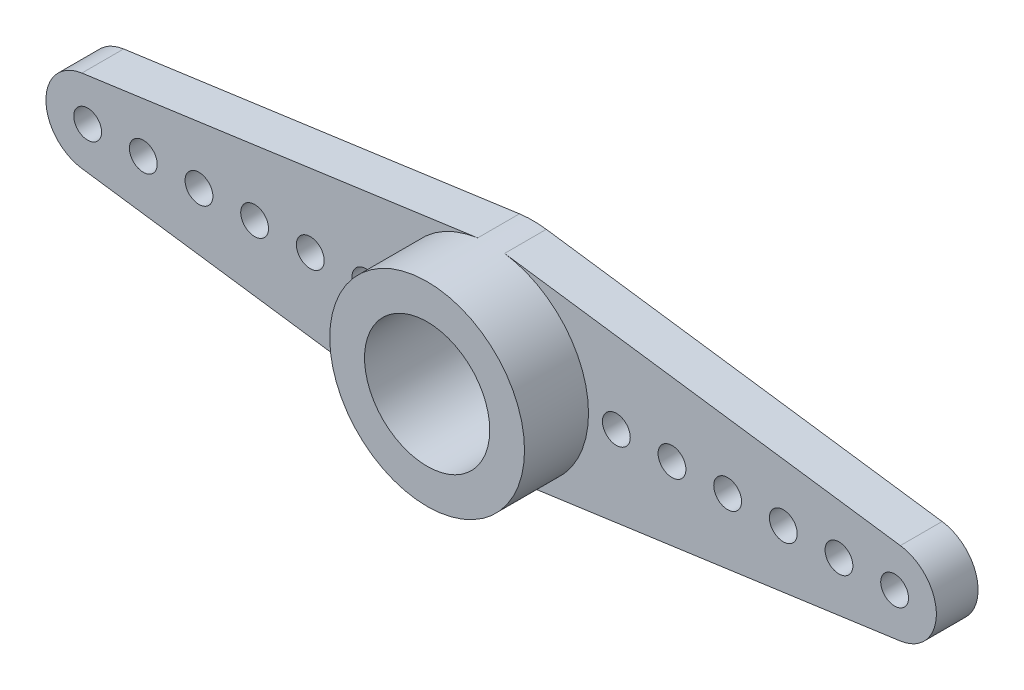
SolidWorks part; units mm, degrees
ref_plane "前视基准面" through (0, 0, 0) normal (0, 0, 1) x (1, 0, 0)
ref_plane "上视基准面" through (0, 0, 0) normal (0, 1, 0) x (1, 0, 0)
ref_plane "右视基准面" through (0, 0, 0) normal (1, 0, 0) x (0, 0, -1)
sketch "草图1" plane through (0, 0, 0) normal (0, 0, 1) x (1, 0, 0)
  line L0 (0, 0) -> (0, -2.5508) construction
  line L1 (-14.5, 0) -> (0, 0) construction
  line L2 (-14.7069, 1.4857) -> (-0.4828, 3.4665)
  line L3 (-14.7069, -1.4857) -> (-0.4828, -3.4665)
  line L4 (14.7069, 1.4857) -> (0.4828, 3.4665)
  line L5 (14.7069, -1.4857) -> (0.4828, -3.4665)
  arc A0 (-0.4828, -3.4665) -> (0.4828, -3.4665) centre (0, 0) ccw
  arc A1 (-14.7069, 1.4857) -> (-14.7069, -1.4857) centre (-14.5, 0) ccw
  arc A2 (14.7069, 1.4857) -> (14.7069, -1.4857) centre (14.5, 0) cw
  arc A3 (0.4828, 3.4665) -> (-0.4828, 3.4665) centre (0, 0) ccw
  point P1 (16, 0)
  point P4 (-16, 0)
  dimension "D1" = 7
  dimension "D3" = 3
  dimension "D2" = 14.5
  dimension "D4" = 32
extrude "凸台-拉伸1" add sketch "草图1" along normal blind 1.5
sketch "草图2" plane through (0, 0, 1.5) normal (0, 0, 1) x (1, 0, 0)
  circle A0 centre (0, 0) radius 3.5
  dimension "D1" = 7
extrude "凸台-拉伸2" add sketch "草图2" along normal blind 2.3
sketch "草图3" plane through (0, 0, 3.8) normal (0, 0, 1) x (1, 0, 0)
  circle A0 centre (0, 0) radius 2.25
  dimension "D1" = 4.5
extrude "切除-拉伸1" cut sketch "草图3" against normal up to surface (3.8 mm away) up to face at (0, 0, 0)
sketch "草图5" plane through (0, 0, 0) normal (0, 0, -1) x (-1, 0, 0)
  line L0 (0, 0) -> (0, -1.4306) construction
  circle A0 centre (-4.5, 0) radius 0.5
  circle A3 centre (-6.5, 0) radius 0.5
  circle A4 centre (-8.5, 0) radius 0.5
  circle A5 centre (-10.5, 0) radius 0.5
  circle A6 centre (-12.5, 0) radius 0.5
  circle A7 centre (-14.5, 0) radius 0.5
  circle A8 centre (4.5, 0) radius 0.5
  circle A9 centre (14.5, 0) radius 0.5
  circle A10 centre (12.5, 0) radius 0.5
  circle A11 centre (10.5, 0) radius 0.5
  circle A12 centre (8.5, 0) radius 0.5
  circle A13 centre (6.5, 0) radius 0.5
  dimension "D2" = 1
  dimension "D1" = 4.5
  dimension "D3" = 6
extrude "切除-拉伸2" cut sketch "草图5" against normal up to surface (1.5 mm away) up to face at (8.6724, 0, 1.5)
